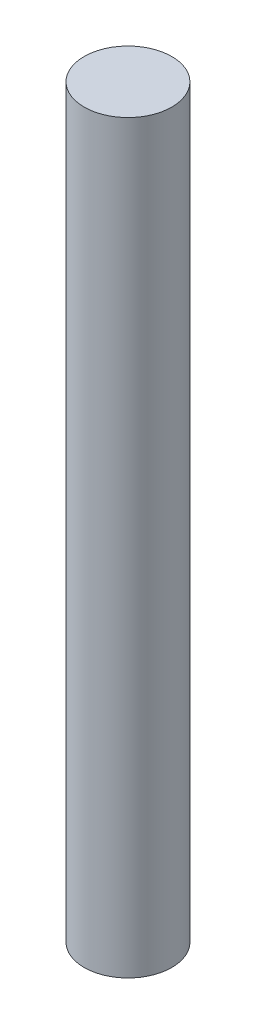
SolidWorks part; units mm, degrees
ref_plane "Front Plane" through (0, 0, 0) normal (0, 0, 1) x (1, 0, 0)
ref_plane "Top Plane" through (0, 0, 0) normal (0, 1, 0) x (1, 0, 0)
ref_plane "Right Plane" through (0, 0, 0) normal (1, 0, 0) x (0, 0, -1)
sketch "Sketch1" plane through (0, 0, 0) normal (0, 1, 0) x (1, 0, 0)
  circle A0 centre (0, 0) radius 2
  dimension "D1" = 4
extrude "Boss-Extrude1" add sketch "Sketch1" along normal mid plane 34
